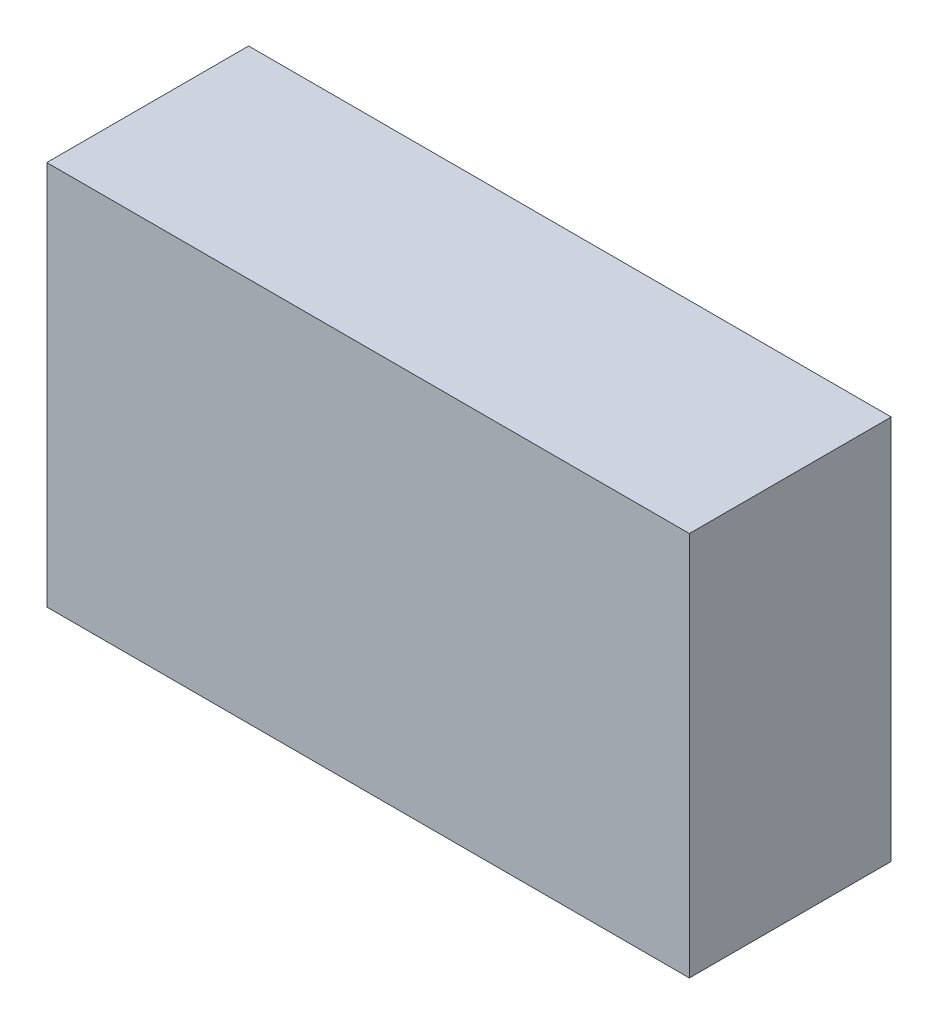
SolidWorks part; units mm, degrees
material "Al-Aly 7075-T7351 Plate per AMS 4078"
ref_plane "Z Plane" through (0, 0, 0) normal (0, 0, 1) x (1, 0, 0)
ref_plane "Y Plane" through (0, 0, 0) normal (0, 1, 0) x (1, 0, 0)
ref_plane "X Plane" through (0, 0, 0) normal (1, 0, 0) x (0, 0, -1)
ref_axis "X Axis" through (-88.99, 0, 0) along (1, 0, 0)
ref_axis "Z Axis" through (0, 0, -88.99) along (0, 0, 1)
ref_axis "Y Axis" through (0, 55, 0) along (0, -1, 0)
sketch "Sketch1" plane through (0, 0, 0) normal (0, 0, 1) x (1, 0, 0)
  line L1 (-80.8622, -48.4364) -> (80.8622, -48.4364)
  line L2 (-80.8622, -48.4364) -> (-80.8622, 48.4364)
  line L3 (-80.8622, 48.4364) -> (80.8622, 48.4364)
  line L4 (80.8622, -48.4364) -> (80.8622, 48.4364)
  line L5 (-80.8622, -48.4364) -> (80.8622, 48.4364) construction
  line L6 (-80.8622, 48.4364) -> (80.8622, -48.4364) construction
  point P0 (0, 0)
extrude "Boss-Extrude1" add sketch "Sketch1" along normal blind 50.8
